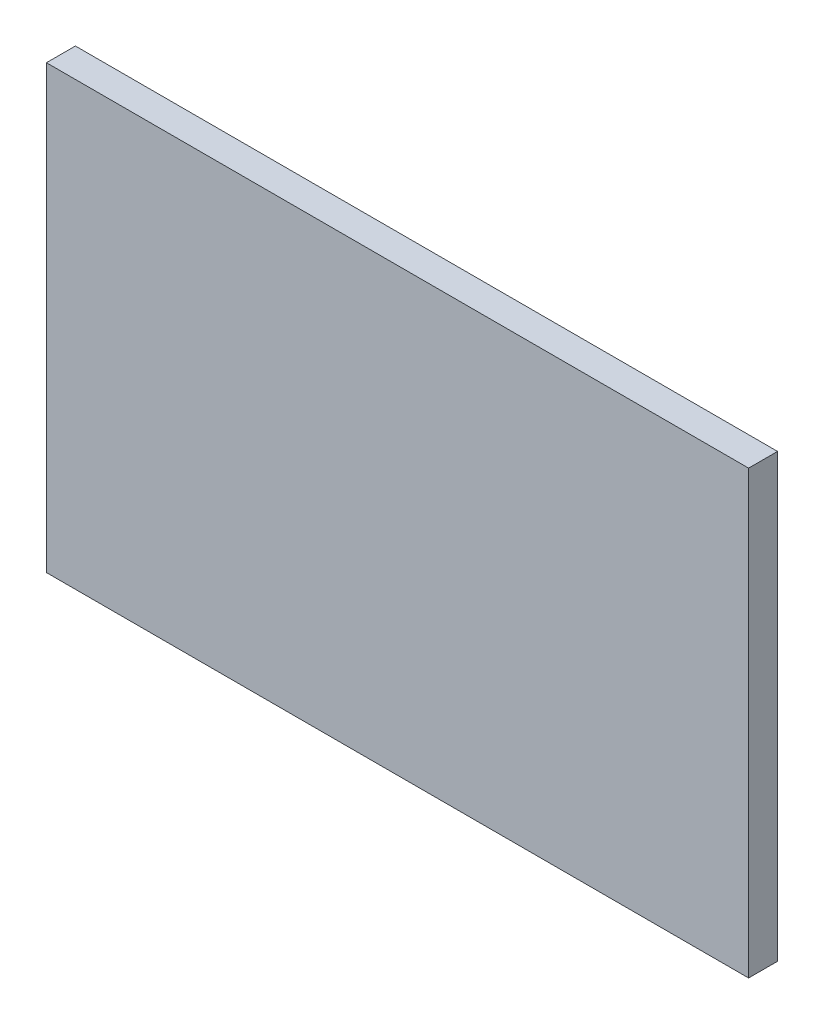
SolidWorks part; units mm, degrees
ref_plane "Front Plane" through (0, 0, 0) normal (0, 0, 1) x (1, 0, 0)
ref_plane "Top Plane" through (0, 0, 0) normal (0, 1, 0) x (1, 0, 0)
ref_plane "Right Plane" through (0, 0, 0) normal (1, 0, 0) x (0, 0, -1)
sketch "Sketch1" plane through (0, 0, 0) normal (0, 0, 1) x (1, 0, 0)
  line L0 (-152.4, 0) -> (155.575, 0) construction
  line L5 (155.575, -88.9) -> (-152.4, -88.9)
  line L7 (155.575, 104.775) -> (-152.4, 104.775)
  line L11 (-152.4, 104.775) -> (-152.4, 0)
  line L12 (-152.4, 0) -> (-152.4, -88.9)
  line L13 (155.575, 104.775) -> (155.575, 0)
  line L14 (155.575, 0) -> (155.575, -88.9)
  point P0 (0, 0)
  dimension "D1" = 307.975
  dimension "D2" = 104.775
  dimension "D3" = 88.9
extrude "Boss-Extrude1" add sketch "Sketch1" along normal blind 12.7
